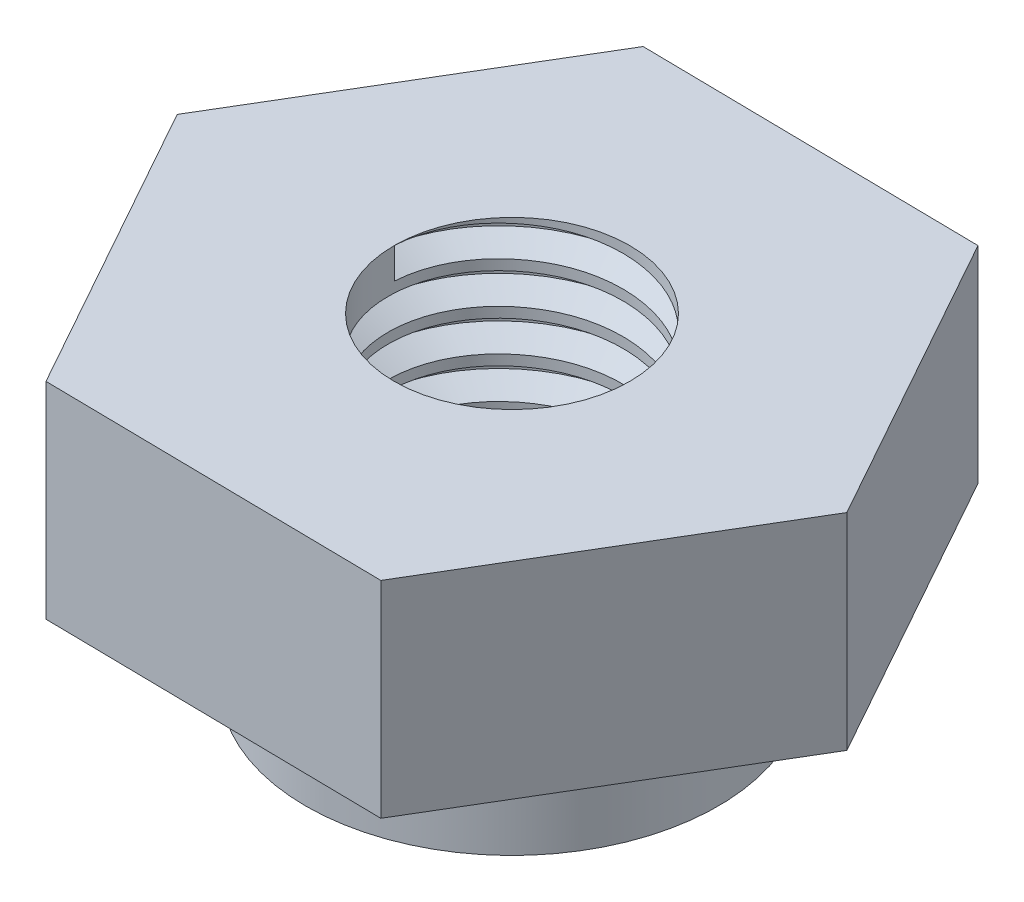
SolidWorks part; units mm, degrees
ref_plane "Alzado" through (0, 0, 0) normal (0, 0, 1) x (1, 0, 0)
ref_plane "Planta" through (0, 0, 0) normal (0, 1, 0) x (1, 0, 0)
ref_plane "Vista lateral" through (0, 0, 0) normal (1, 0, 0) x (0, 0, -1)
sketch "Croquis1" plane through (0, 0, 0) normal (0, 1, 0) x (1, 0, 0)
  line L1 (2.9596, 4.9573) -> (-2.8133, 5.0417)
  line L2 (-2.8133, 5.0417) -> (-5.7729, 0.0844)
  line L3 (-5.7729, 0.0844) -> (-2.9596, -4.9573)
  line L4 (-2.9596, -4.9573) -> (2.8133, -5.0417)
  line L5 (2.8133, -5.0417) -> (5.7729, -0.0844)
  line L6 (5.7729, -0.0844) -> (2.9596, 4.9573)
  circle A0 centre (0, 0) radius 5 construction
  circle A1 centre (0, 0) radius 2
  dimension "D1" = 10
  dimension "D2" = 4
extrude "Saliente-Extruir1" add sketch "Croquis1" along normal blind 3.5
thread "Rosca1" pitch 0.7 method cut profile "Perfil de rosca1" start angle 0, offset 0, length 0, pitch 0.7, diameter 4
ref_plane "Plano1" through (-2, 3.5, 0) normal (0, 0, 1) x (-1, 0, 0)
sketch "Perfil de rosca1" plane through (-2, 3.5, 0) normal (0, 0, 1) x (-1, 0, 0)
  line L0 (0, 0) -> (0, 0.7) construction
  line L1 (0, 0) -> (0.3789, 0.2187)
  line L2 (0.3789, 0.2187) -> (0.3789, 0.3062)
  line L3 (0.3789, 0.3062) -> (0, 0.525)
  line L4 (0.3789, 0.2625) -> (0, 0.2625) construction
  line L11 (0, 0) -> (0, 0.525)
  point P2 (0, 0)
  dimension "Pitch" = 0.7
  dimension "Profile_Angle" = 60
  dimension "Profile_Land" = 0.0875
  dimension "Profile_Height" = 0.3789
sketch "Croquis2" plane through (0, 0, 0) normal (0, -1, 0) x (1, 0, 0)
  circle A0 centre (0, 0) radius 2.25
  circle A1 centre (0, 0) radius 3.5
  dimension "D1" = 7
  dimension "D2" = 4.5
extrude "Saliente-Extruir2" add sketch "Croquis2" along normal blind 2
